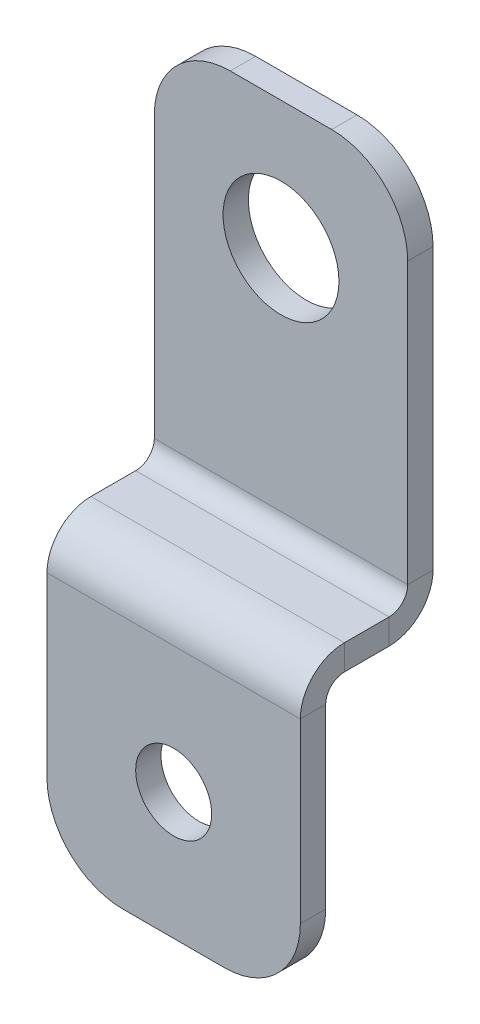
SolidWorks part; units mm, degrees
note: The reader was unsure of these and kept them because the rebuilt part matched: flange length of "Edge-Flange1", "Edge-Flange2".
ref_plane "Ön Düzlem" through (0, 0, 0) normal (0, 0, 1) x (1, 0, 0)
ref_plane "Üst Düzlem" through (0, 0, 0) normal (0, 1, 0) x (1, 0, 0)
ref_plane "Sağ Düzlem" through (0, 0, 0) normal (1, 0, 0) x (0, 0, -1)
sketch "Sketch1" plane through (0, 0, 0) normal (0, 0, 1) x (1, 0, 0)
  line L1 (-514.9742, -14.3503) -> (-504.9742, -14.3503)
  line L2 (-514.9742, -14.3503) -> (-514.9742, -28.4078)
  line L3 (-514.9742, -28.4078) -> (-504.9742, -28.4078)
  line L4 (-504.9742, -14.3503) -> (-504.9742, -28.4078)
  line L6 (-509.9742, -19.4) -> (-504.9742, -19.4) construction
  line L7 (-509.9742, -19.4) -> (-514.9742, -19.4) construction
  circle A0 centre (-509.9742, -19.4) radius 2.2873
  dimension "D1" = 10
base flange "Base-Flange1" sketch "Sketch1" thickness 1 reverse thickness direction yes parameters "D1"=0.7366
edge flange "Edge-Flange1" sketch "Sketch8" flange angle 90 flange length 3.5 flange position bend outside bend radius 0.7366 thickness 1 relief rectangular parameters "D6"=10
sketch "Sketch8" plane through (0, -28.4078, 1) normal (0, -1, 0) x (1, 0, 0)
  line L0 (-514.9742, 0) -> (-504.9742, 0) construction
  line L1 (-514.9742, 0) -> (-504.9742, 0)
  line L2 (-514.9742, 0) -> (-514.9742, 2.5)
  line L3 (-514.9742, 2.5) -> (-504.9742, 2.5)
  line L4 (-504.9742, 2.5) -> (-504.9742, 0)
bend "EdgeBend1" bend radius 0.7366 bend angle 90 parameters "D5"=1
edge flange "Edge-Flange2" sketch "Sketch11" flange angle 90 flange length 11.7366 flange position bend outside bend radius 0.7366 thickness 1 relief rectangular parameters "D6"=10
sketch "Sketch11" plane through (0, -30.1444, 3.5) normal (0, 0, 1) x (-1, 0, 0)
  line L0 (504.9742, 0) -> (514.9742, 0) construction
  line L1 (504.9742, 0) -> (514.9742, 0)
  line L2 (504.9742, 0) -> (504.9742, 10.7366)
  line L3 (504.9742, 10.7366) -> (514.9742, 10.7366)
  line L4 (514.9742, 10.7366) -> (514.9742, 0)
bend "EdgeBend2" bend radius 0.7366 bend angle 90 parameters "D5"=2
sketch "Sketch12" plane through (0, 0, 4.2366) normal (0, 0, -1) x (-1, 0, 0)
  line L0 (509.9742, -30.881) -> (509.9742, -40.881) construction
  line L1 (504.9742, -30.881) -> (514.9742, -30.881) construction
  line L2 (514.9742, -40.881) -> (504.9742, -40.881) construction
  circle A0 centre (509.9742, -35.881) radius 1.5
  dimension "D1" = 3
extrude "Cut-Extrude1" cut sketch "Sketch12" against normal blind 2 normal cut yes
fillet "Fillet1" radius 3 4 edges at (-514.9742, -14.3503, 0.5) (-504.9742, -14.3503, 0.5) (-504.9742, -40.881, 4.7366) (-514.9742, -40.881, 4.7366)
sketch "Büküm-Çizgileri1" [suppressed] plane through (0, 0, 0) normal (0, 1, 0) x (1, 0, 0)
sketch "Sınırlandırma-Kutusu1" [suppressed] plane through (0, 0, 0) normal (0, 1, 0) x (1, 0, 0)
sheet metal parameters "Sheet-Metal2" thickness 1 parameters "D1"=0.7366
flat pattern "Flat-Pattern2" [suppressed]
sketch "Büküm-Çizgileri2" plane through (0, 0, 0) normal (0, 1, 0) x (1, 0, 0)
sketch3d "Sınırlandırma-Kutusu2" [suppressed]
  line L0 (517.4041, -28.4078, 0) -> (502.5443, -28.4078, 0) construction
  line L1 (517.4041, -14.3503, 0) -> (502.5443, -14.3503, 0) construction
  line L2 (517.4041, -28.4078, 0) -> (517.4041, -14.3503, 0) construction
  line L3 (502.5443, -28.4078, 0) -> (502.5443, -14.3503, 0) construction
sheet metal parameters "Sheet-Metal3" thickness 1 parameters "D1"=0.7366
flat pattern "Flat-Pattern2"
sketch "Büküm-Çizgileri2" plane through (0, 0, 0) normal (0, 0, -1) x (-1, 0, 0)
  line L0 (502.5443, -29.379) -> (517.4041, -29.379) construction
  line L1 (502.5443, -29.379) -> (517.4041, -29.379) construction
sketch3d "Sınırlandırma-Kutusu2" [suppressed]
  line L0 (502.5443, -14.3503, 0) -> (502.5443, -33.6137, 0) construction
  line L1 (517.4041, -14.3503, 0) -> (517.4041, -33.6137, 0) construction
  line L2 (502.5443, -14.3503, 0) -> (517.4041, -14.3503, 0) construction
  line L3 (502.5443, -33.6137, 0) -> (517.4041, -33.6137, 0) construction
bend of the flat pattern "Flatten-<EdgeBend1>1"
sheet metal parameters "Sheet-Metal4" thickness 1 parameters "D1"=0.7366
flat pattern "Flat-Pattern2"
sketch "Büküm-Çizgileri2" plane through (0, 0, 0) normal (0, 0, -1) x (-1, 0, 0)
  line L0 (502.5443, -29.379) -> (517.4041, -29.379) construction
  line L1 (502.5443, -29.379) -> (517.4041, -29.379) construction
  line L2 (502.5443, -34.5849) -> (517.4041, -34.5849) construction
  line L3 (502.5443, -34.5849) -> (517.4041, -34.5849) construction
sketch3d "Sınırlandırma-Kutusu2" [suppressed]
  line L0 (502.5443, -14.3503, 0) -> (502.5443, -45.5561, 0) construction
  line L1 (517.4041, -14.3503, 0) -> (517.4041, -45.5561, 0) construction
  line L2 (502.5443, -14.3503, 0) -> (517.4041, -14.3503, 0) construction
  line L3 (502.5443, -45.5561, 0) -> (517.4041, -45.5561, 0) construction
bend of the flat pattern "Flatten-<EdgeBend1>1"
bend of the flat pattern "Flatten-<EdgeBend2>1"
sheet metal parameters "Sheet-Metal5" thickness 1 parameters "D1"=0.7366
flat pattern "Flat-Pattern2"
sketch "Büküm-Çizgileri2" plane through (0, 0, 0) normal (0, 0, -1) x (-1, 0, 0)
  line L0 (504.9742, -29.379) -> (514.9742, -29.379) construction
  line L1 (504.9742, -29.379) -> (514.9742, -29.379) construction
  line L2 (504.9742, -33.0849) -> (514.9742, -33.0849) construction
  line L3 (504.9742, -33.0849) -> (514.9742, -33.0849) construction
sketch3d "Sınırlandırma-Kutusu2" [suppressed]
  line L0 (504.9742, -14.3503, 0) -> (504.9742, -44.0561, 0) construction
  line L1 (514.9742, -14.3503, 0) -> (514.9742, -44.0561, 0) construction
  line L2 (504.9742, -14.3503, 0) -> (514.9742, -14.3503, 0) construction
  line L3 (504.9742, -44.0561, 0) -> (514.9742, -44.0561, 0) construction
bend of the flat pattern "Flatten-<EdgeBend1>1"
bend of the flat pattern "Flatten-<EdgeBend2>1"
